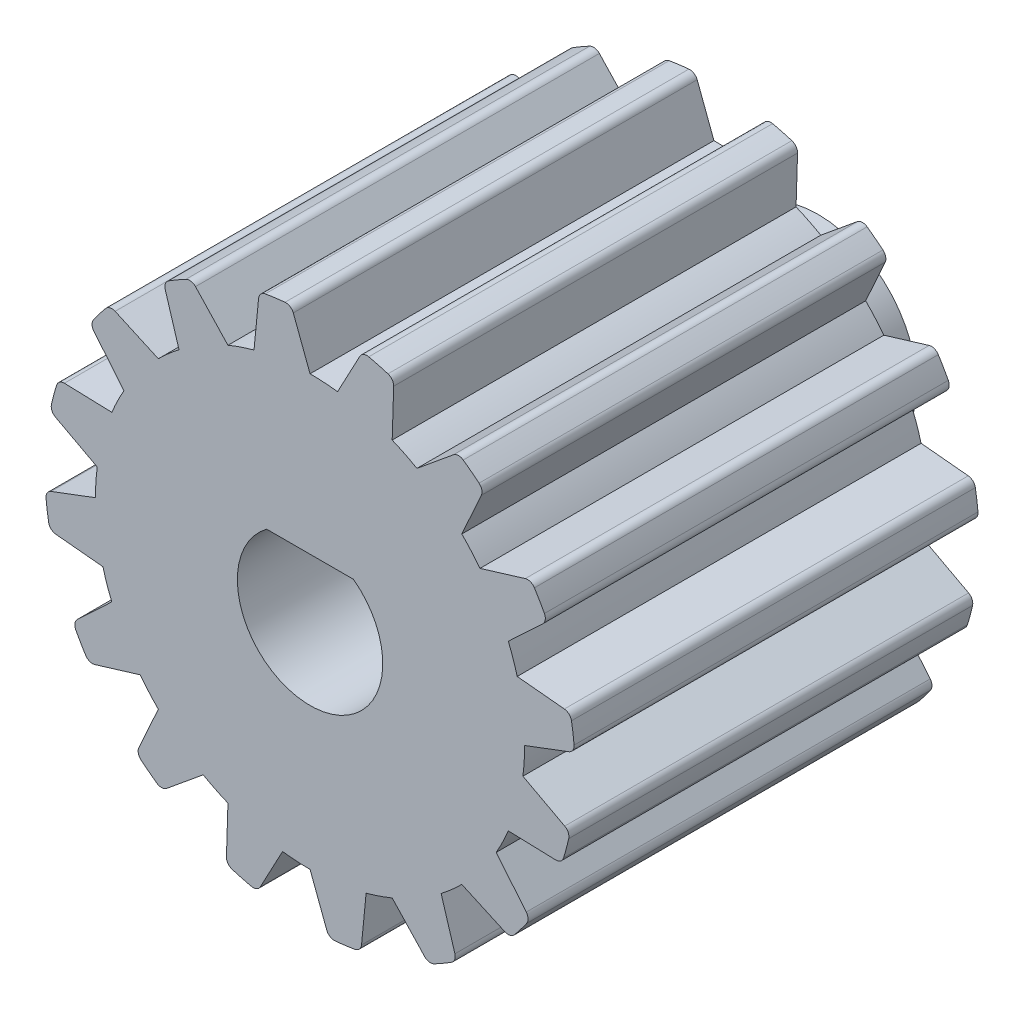
SolidWorks part; units mm, degrees
ref_plane "Alzado" through (0, 0, 0) normal (0, 0, 1) x (1, 0, 0)
ref_plane "Planta" through (0, 0, 0) normal (0, 1, 0) x (1, 0, 0)
ref_plane "Vista lateral" through (0, 0, 0) normal (1, 0, 0) x (0, 0, -1)
sketch "Croquis2" plane through (0, 0, 0) normal (0, 0, 1) x (1, 0, 0)
  line L0 (0, 0) -> (0, 7.9702) construction
  line L2 (-2.0817, 7.6936) -> (-1.9112, 9.4453)
  line L3 (-1.0408, 7.8319) -> (0, 0) construction
  line L4 (0, 7.9702) -> (-0.6221, 9.6166)
  line L5 (1.021, 7.9046) -> (1.8489, 9.4577)
  line L6 (3.0501, 7.3635) -> (3.1053, 9.1227)
  line L7 (3.9682, 6.9122) -> (5.3274, 8.0302)
  line L8 (5.6358, 5.6358) -> (6.3601, 7.2399)
  line L9 (6.3113, 4.8674) -> (7.9949, 5.3803)
  line L10 (7.3635, 3.0501) -> (8.6465, 4.2549)
  line L11 (7.6936, 2.0817) -> (9.4453, 1.9112)
  line L12 (7.9702, 0) -> (9.6166, 0.6221)
  line L13 (7.9046, -1.021) -> (9.4577, -1.8489)
  line L14 (7.3635, -3.0501) -> (9.1227, -3.1053)
  line L15 (6.9122, -3.9682) -> (8.0302, -5.3274)
  line L16 (5.6358, -5.6358) -> (7.2399, -6.3601)
  line L17 (4.8674, -6.3113) -> (5.3803, -7.9949)
  line L18 (3.0501, -7.3635) -> (4.2549, -8.6465)
  line L19 (2.0817, -7.6936) -> (1.9112, -9.4453)
  line L20 (0, -7.9702) -> (0.6221, -9.6166)
  line L21 (-1.021, -7.9046) -> (-1.8489, -9.4577)
  line L22 (-3.0501, -7.3635) -> (-3.1053, -9.1227)
  line L23 (-3.9682, -6.9122) -> (-5.3274, -8.0302)
  line L24 (-5.6358, -5.6358) -> (-6.3601, -7.2399)
  line L25 (-6.3113, -4.8674) -> (-7.9949, -5.3803)
  line L26 (-7.3635, -3.0501) -> (-8.6465, -4.2549)
  line L27 (-7.6936, -2.0817) -> (-9.4453, -1.9112)
  line L28 (-7.9702, 0) -> (-9.6166, -0.6221)
  line L29 (-7.9046, 1.021) -> (-9.4577, 1.8489)
  line L30 (-7.3635, 3.0501) -> (-9.1227, 3.1053)
  line L31 (-6.9122, 3.9682) -> (-8.0302, 5.3274)
  line L32 (-5.6358, 5.6358) -> (-7.2399, 6.3601)
  line L33 (-4.8674, 6.3113) -> (-5.3803, 7.9949)
  line L34 (-3.0501, 7.3635) -> (-4.2549, 8.6465)
  arc A0 (-4.8674, 6.3113) -> (-5.6358, 5.6358) centre (0, 0) ccw
  arc A1 (-7.5914, 6.2764) -> (-8.0413, 5.6886) centre (0, 0) ccw
  arc A2 (-1.6636, 9.7085) -> (-1.9112, 9.4453) centre (-1.6129, 9.4128) ccw
  arc A3 (-0.9298, 9.806) -> (-0.6221, 9.6166) centre (-0.9015, 9.5074) cw
  arc A4 (2.1783, 9.6061) -> (1.8489, 9.4577) centre (2.112, 9.3135) ccw
  arc A5 (2.8935, 9.4154) -> (3.1053, 9.1227) centre (2.8054, 9.1286) cw
  arc A6 (5.6886, 8.0413) -> (5.3274, 8.0302) centre (5.5153, 7.7964) ccw
  arc A7 (6.2764, 7.5914) -> (6.3601, 7.2399) centre (6.0852, 7.3602) cw
  arc A8 (8.3328, 5.2523) -> (7.9949, 5.3803) centre (8.0791, 5.0923) ccw
  arc A9 (8.7037, 4.6117) -> (8.6465, 4.2549) centre (8.4387, 4.4712) cw
  arc A10 (9.7085, 1.6636) -> (9.4453, 1.9112) centre (9.4128, 1.6129) ccw
  arc A11 (9.806, 0.9298) -> (9.6166, 0.6221) centre (9.5074, 0.9015) cw
  arc A12 (9.6061, -2.1783) -> (9.4577, -1.8489) centre (9.3135, -2.112) ccw
  arc A13 (9.4154, -2.8935) -> (9.1227, -3.1053) centre (9.1286, -2.8054) cw
  arc A14 (8.0413, -5.6886) -> (8.0302, -5.3274) centre (7.7964, -5.5153) ccw
  arc A15 (7.5914, -6.2764) -> (7.2399, -6.3601) centre (7.3602, -6.0852) cw
  arc A16 (5.2523, -8.3328) -> (5.3803, -7.9949) centre (5.0923, -8.0791) ccw
  arc A17 (4.6117, -8.7037) -> (4.2549, -8.6465) centre (4.4712, -8.4387) cw
  arc A18 (1.6636, -9.7085) -> (1.9112, -9.4453) centre (1.6129, -9.4128) ccw
  arc A19 (0.9298, -9.806) -> (0.6221, -9.6166) centre (0.9015, -9.5074) cw
  arc A20 (-2.1783, -9.6061) -> (-1.8489, -9.4577) centre (-2.112, -9.3135) ccw
  arc A21 (-2.8935, -9.4154) -> (-3.1053, -9.1227) centre (-2.8054, -9.1286) cw
  arc A22 (-5.6886, -8.0413) -> (-5.3274, -8.0302) centre (-5.5153, -7.7964) ccw
  arc A23 (-6.2764, -7.5914) -> (-6.3601, -7.2399) centre (-6.0852, -7.3602) cw
  arc A24 (-8.3328, -5.2523) -> (-7.9949, -5.3803) centre (-8.0791, -5.0923) ccw
  arc A25 (-8.7037, -4.6117) -> (-8.6465, -4.2549) centre (-8.4387, -4.4712) cw
  arc A26 (-9.7085, -1.6636) -> (-9.4453, -1.9112) centre (-9.4128, -1.6129) ccw
  arc A27 (-9.806, -0.9298) -> (-9.6166, -0.6221) centre (-9.5074, -0.9015) cw
  arc A28 (-9.6061, 2.1783) -> (-9.4577, 1.8489) centre (-9.3135, 2.112) ccw
  arc A29 (-9.4154, 2.8935) -> (-9.1227, 3.1053) centre (-9.1286, 2.8054) cw
  arc A30 (-8.0413, 5.6886) -> (-8.0302, 5.3274) centre (-7.7964, 5.5153) ccw
  arc A31 (-7.5914, 6.2764) -> (-7.2399, 6.3601) centre (-7.3602, 6.0852) cw
  arc A32 (-5.2523, 8.3328) -> (-5.3803, 7.9949) centre (-5.0923, 8.0791) ccw
  arc A33 (-4.6117, 8.7037) -> (-4.2549, 8.6465) centre (-4.4712, 8.4387) cw
  arc A34 (-4.6117, 8.7037) -> (-5.2523, 8.3328) centre (0, 0) ccw
  arc A35 (-0.9298, 9.806) -> (-1.6636, 9.7085) centre (0, 0) ccw
  arc A36 (2.8935, 9.4154) -> (2.1783, 9.6061) centre (0, 0) ccw
  arc A37 (6.2764, 7.5914) -> (5.6886, 8.0413) centre (0, 0) ccw
  arc A38 (8.7037, 4.6117) -> (8.3328, 5.2523) centre (0, 0) ccw
  arc A39 (9.4154, -2.8935) -> (9.6061, -2.1783) centre (0, 0) ccw
  arc A40 (7.5914, -6.2764) -> (8.0413, -5.6886) centre (0, 0) ccw
  arc A41 (-9.4154, 2.8935) -> (-9.6061, 2.1783) centre (0, 0) ccw
  arc A42 (-9.806, -0.9298) -> (-9.7085, -1.6636) centre (0, 0) ccw
  arc A43 (-8.7037, -4.6117) -> (-8.3328, -5.2523) centre (0, 0) ccw
  arc A44 (-6.2764, -7.5914) -> (-5.6886, -8.0413) centre (0, 0) ccw
  arc A45 (-2.8935, -9.4154) -> (-2.1783, -9.6061) centre (0, 0) ccw
  arc A46 (0.9298, -9.806) -> (1.6636, -9.7085) centre (0, 0) ccw
  arc A47 (4.6117, -8.7037) -> (5.2523, -8.3328) centre (0, 0) ccw
  arc A48 (-2.0817, 7.6936) -> (-3.0501, 7.3635) centre (0, 0) ccw
  arc A49 (1.021, 7.9046) -> (0, 7.9702) centre (0, 0) ccw
  arc A50 (3.9682, 6.9122) -> (3.0501, 7.3635) centre (0, 0) ccw
  arc A51 (6.3113, 4.8674) -> (5.6358, 5.6358) centre (0, 0) ccw
  arc A52 (7.6936, 2.0817) -> (7.3635, 3.0501) centre (0, 0) ccw
  arc A53 (7.9046, -1.021) -> (7.9702, 0) centre (0, 0) ccw
  arc A54 (9.806, 0.9298) -> (9.7085, 1.6636) centre (0, 0) ccw
  arc A55 (6.9122, -3.9682) -> (7.3635, -3.0501) centre (0, 0) ccw
  arc A56 (4.8674, -6.3113) -> (5.6358, -5.6358) centre (0, 0) ccw
  arc A57 (2.0817, -7.6936) -> (3.0501, -7.3635) centre (0, 0) ccw
  arc A58 (-1.021, -7.9046) -> (0, -7.9702) centre (0, 0) ccw
  arc A59 (-3.9682, -6.9122) -> (-3.0501, -7.3635) centre (0, 0) ccw
  arc A60 (-6.3113, -4.8674) -> (-5.6358, -5.6358) centre (0, 0) ccw
  arc A61 (-7.6936, -2.0817) -> (-7.3635, -3.0501) centre (0, 0) ccw
  arc A62 (-7.9046, 1.021) -> (-7.9702, 0) centre (0, 0) ccw
  arc A63 (-6.9122, 3.9682) -> (-7.3635, 3.0501) centre (0, 0) ccw
  dimension "D1" = 2.1
  dimension "D2" = 19.7
  dimension "D3" = 15.9404
  dimension "D6" = 0.6
  dimension "D4" = 1.76
extrude "Saliente-Extruir1" add sketch "Croquis2" along normal blind 15
sketch "Croquis3" plane through (0, 0, 15) normal (0, 0, 1) x (1, 0, 0)
  line L0 (0, 0) -> (0, 1.68) construction
  line L1 (-1.4967, 1.68) -> (1.4967, 1.68)
  arc A0 (-1.4967, 1.68) -> (1.4967, 1.68) centre (0, 0) ccw
  point P7 (0, 1.68)
  dimension "D1" = 4.5
  dimension "D2" = 1.68
sketch "Croquis5" plane through (0, 0, 0) normal (0, 0, -1) x (-1, 0, 0)
  circle A0 centre (0, 0) radius 4.5
  dimension "D1" = 9
extrude "Saliente-Extruir2" add sketch "Croquis5" along normal blind 6
extrude "Cortar-Extruir1" cut sketch "Croquis3" against normal through all
scale "Escala1" scale about origin uniform scaling yes scale factor 1.5
sketch "Croquis6" plane through (0, 0, 22.5) normal (0, 0, 1) x (1, 0, 0)
  line L0 (0, -4.05) -> (0, 3.25) construction
  line L1 (2.4166, 3.25) -> (-2.4166, 3.25)
  arc A0 (-2.245, 2.52) -> (2.245, 2.52) centre (0, 0) ccw construction
  arc A1 (-2.245, 2.52) -> (2.245, 2.52) centre (0, 0) ccw construction
  arc A2 (-2.4166, 3.25) -> (2.4166, 3.25) centre (0, 0) ccw
  dimension "D1" = 8.1
  dimension "D2" = 7.3
extrude "Cortar-Extruir2" cut sketch "Croquis6" against normal through all both and the other way through all
sketch "Croquis7" plane through (0, 0, -9) normal (0, 0, -1) x (-1, 0, 0)
  circle A0 centre (0, 0) radius 10
  dimension "D1" = 20
extrude "Cortar-Extruir3" cut sketch "Croquis7" against normal blind 5.8 and the other way through all
sketch "Croquis8" plane through (0, 0, -3.2) normal (0, 0, -1) x (-1, 0, 0)
  line L0 (-2.4166, 3.25) -> (2.4166, 3.25) construction
  line L1 (-2.4166, 3.25) -> (2.4166, 3.25)
  arc A1 (-2.4166, 3.25) -> (2.4166, 3.25) centre (0, 0) ccw construction
  arc A2 (-2.4166, 3.25) -> (2.4166, 3.25) centre (0, 0) ccw
  circle A3 centre (0, 0) radius 5.5
  dimension "D1" = 11
extrude "Saliente-Extruir3" add sketch "Croquis8" along normal blind 2.6
